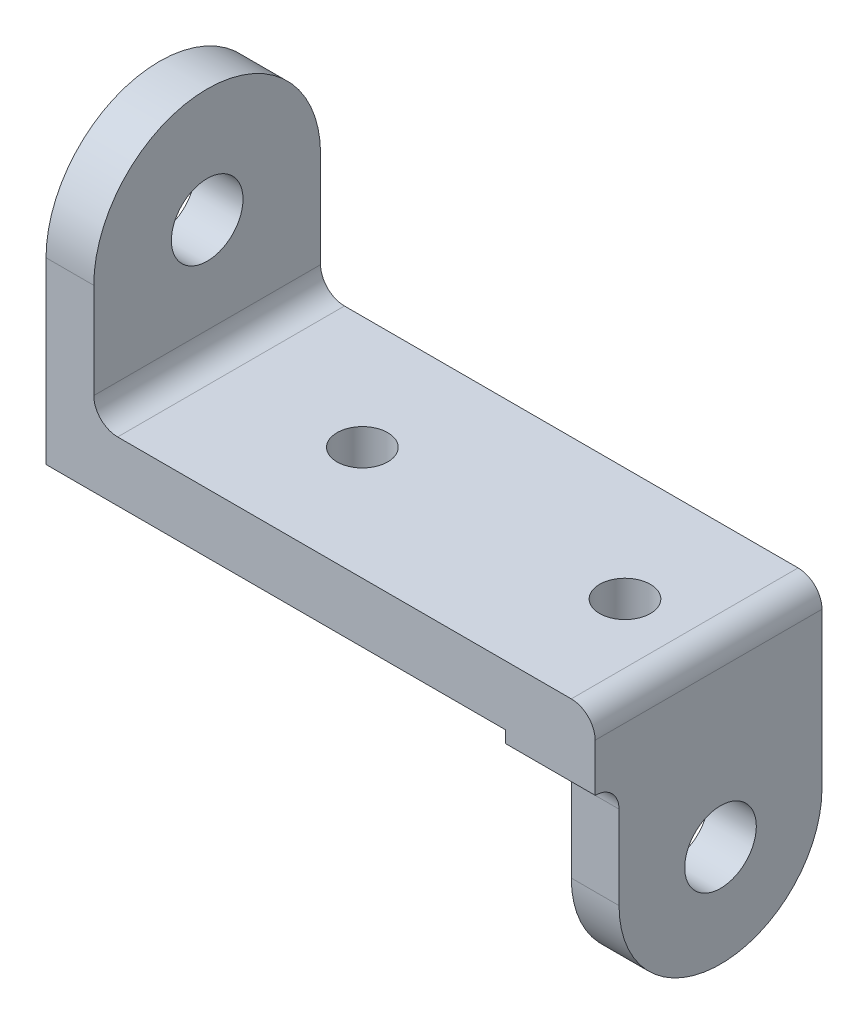
SolidWorks part; units mm, degrees
ref_plane "Front Plane" through (0, 0, 0) normal (0, 0, 1) x (1, 0, 0)
ref_plane "Top Plane" through (0, 0, 0) normal (0, 1, 0) x (1, 0, 0)
ref_plane "Right Plane" through (0, 0, 0) normal (1, 0, 0) x (0, 0, -1)
sketch "Sketch2" plane through (0, 0, 0) normal (1, 0, 0) x (0, 0, -1)
  line L0 (0, 0) -> (0, -3.175)
  line L1 (0, 0) -> (60.325, 0)
  line L2 (0, 0) -> (0, 15.875)
  line L3 (0, 15.875) -> (60.325, 15.875)
  line L4 (60.325, 0) -> (60.325, 15.875)
  line L5 (60.325, 0) -> (60.325, -31.75)
  line L6 (6.35, -9.525) -> (6.35, -31.75)
  line L7 (60.325, -4.7625) -> (4.4901, -5.0349)
  line L8 (0, 15.875) -> (0, 47.625)
  line L9 (60.325, 15.875) -> (60.325, 47.625)
  circle A0 centre (33.3375, -31.75) radius 26.9875
  arc A1 (6.35, -9.525) -> (0, -3.175) centre (0, -9.525) ccw
  circle A2 centre (33.3375, -31.75) radius 19.05
  circle A3 centre (33.3375, -31.75) radius 9.525
  arc A4 (60.325, 47.625) -> (0, 47.625) centre (30.1625, 47.625) ccw
  circle A5 centre (30.1625, 47.625) radius 9.525
  dimension "D3" = 19.05
  dimension "D5" = 6.35
  dimension "D6" = 12.7
  dimension "D7" = 6.35
  dimension "D8" = 38.1
  dimension "D9" = 19.05
  dimension "D11" = 19.05
  dimension "D12" = 31.75
  dimension "D1" = 60.325
  dimension "D2" = 15.875
  dimension "D4" = 31.75
  dimension "D10" = 26.9875
  dimension "D13" = 0.279
extrude "Boss-Extrude1" add sketch "Sketch2" along normal blind 12.7 contours L9 A4 L8 L3 A5 | L1 L4 L3 L2 region at (0, 7.9375, -30.1625) region at (0, 31.75, -0.8644)
extrude "Boss-Extrude2" add sketch "Sketch2<4>" along normal blind 122.2375 contours L1 L4 L3 L2 region at (0, 7.9375, -30.1625)
sketch "Sketch2<4>" plane through (0, 0, 0) normal (1, 0, 0) x (0, 0, -1) same geometry as "Sketch2"
extrude "Boss-Extrude4" add sketch "Sketch2<7>" along normal blind 23.8125 from offset 122.2375 contours A1 L7 A0 L5 L1 L0 | L1 L4 L3 L2 | L7 A0 region at (0, -2.415, -30.4191) region at (0, 7.9375, -30.1625) region at (0, -4.842, -33.2062)
sketch "Sketch2<7>" plane through (0, 0, 0) normal (1, 0, 0) x (0, 0, -1) same geometry as "Sketch2"
extrude "Boss-Extrude5" add sketch "Sketch2<9>" along normal blind 12.7 from offset 133.35 contours A1 L6 A0 L7 | A0 L7 A2 | A2 A3 | A0 L5 L7 region at (0, -10.9071, -12.0928) region at (0, -10.851, -54.4061) region at (0, -5.6573, -33.2102) region at (0, -31.75, -14.8263)
sketch "Sketch2<9>" plane through (0, 0, 0) normal (1, 0, 0) x (0, 0, -1) same geometry as "Sketch2"
fillet "Fillet1" radius 6.35 2 edges at (12.7, 15.875, -30.1625) (146.05, 15.875, -30.1625)
sketch "Sketch3" plane through (0, 15.875, 0) normal (0, 1, 0) x (1, 0, 0)
  line L0 (19.05, 30.1625) -> (139.7, 30.1625) construction
  line L3 (12.7, 0) -> (19.05, 0) construction
  line L4 (139.7, 0) -> (19.05, 0) construction
  circle A0 centre (53.975, 30.1625) radius 6.7469
  circle A1 centre (123.825, 30.1625) radius 6.7469
  point P10 (15.875, 0)
  dimension "D1" = 13.4937
  dimension "D2" = 13.4937
  dimension "D3" = 41.275
  dimension "D4" = 69.85
  dimension "D5" = 30.1625
extrude "Cut-Extrude1" cut sketch "Sketch3" against normal through all
